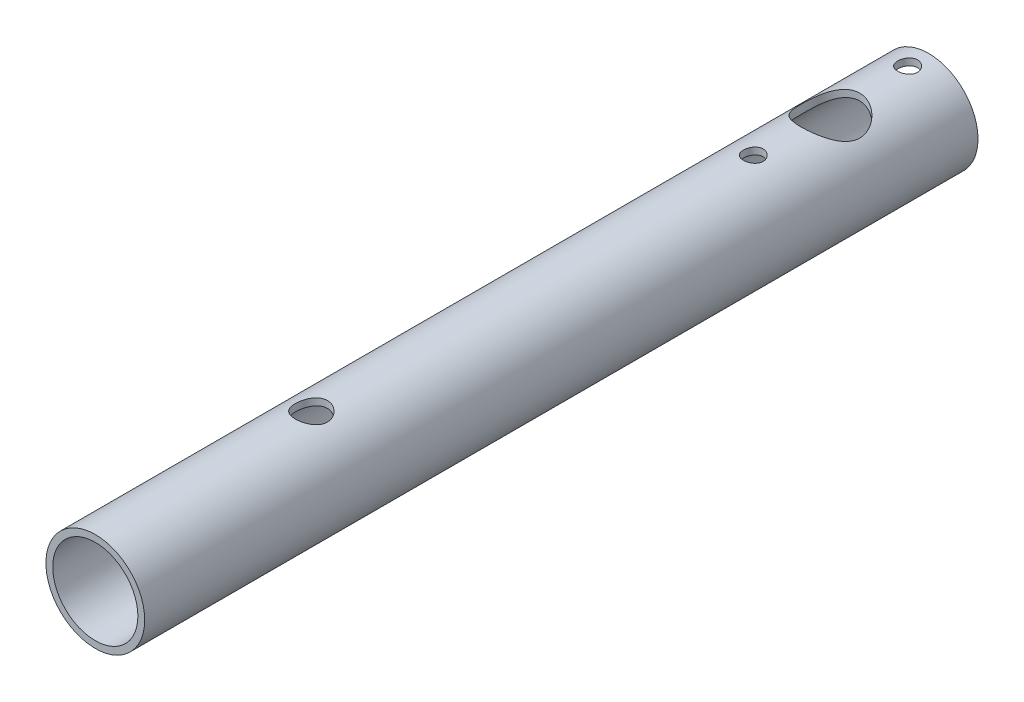
SolidWorks part; units mm, degrees
ref_plane "Front Plane" through (0, 0, 0) normal (0, 0, 1) x (1, 0, 0)
ref_plane "Top Plane" through (0, 0, 0) normal (0, 1, 0) x (1, 0, 0)
ref_plane "Right Plane" through (0, 0, 0) normal (1, 0, 0) x (0, 0, -1)
sketch "Sketch1" plane through (0, 0, 0) normal (0, 0, 1) x (1, 0, 0)
  circle A0 centre (0, 0) radius 8
  circle A1 centre (0, 0) radius 6.9
  dimension "D1" = 16
  dimension "D2" = 13.8
extrude "Boss-Extrude1" add sketch "Sketch1" along normal blind 135
sketch "Sketch2" plane through (0, 0, 0) normal (0, 1, 0) x (1, 0, 0)
  circle A0 centre (0, 0) radius 2.5
  dimension "D1" = 5
extrude "Boss-Extrude2" [suppressed] add sketch "Sketch2" along normal blind 8 and the other way blind 8
sketch "Sketch3" plane through (0, 0, 0) normal (0, 1, 0) x (1, 0, 0)
  line L0 (-8, -135) -> (8, -135) construction
  line L1 (0, -100) -> (0, -135) construction
  line L2 (0, 0) -> (0, -15.9069) construction
  line L3 (6.9, 0) -> (-6.9, 0) construction
  circle A0 centre (0, -100) radius 2.6
  circle A1 centre (0, -15.9069) radius 4.75
  circle A2 centre (0, -3.4069) radius 1.6 construction
  circle A3 centre (0, -28.4069) radius 1.6 construction
  circle A4 centre (0, -3.4069) radius 1.6
  circle A5 centre (0, -28.4069) radius 1.6
  dimension "D2" = 5.2
  dimension "D3" = 9.5
  dimension "D1" = 35
  dimension "D4" = 130
extrude "Cut-Extrude1" cut sketch "Sketch3" against normal through all and the other way through all
